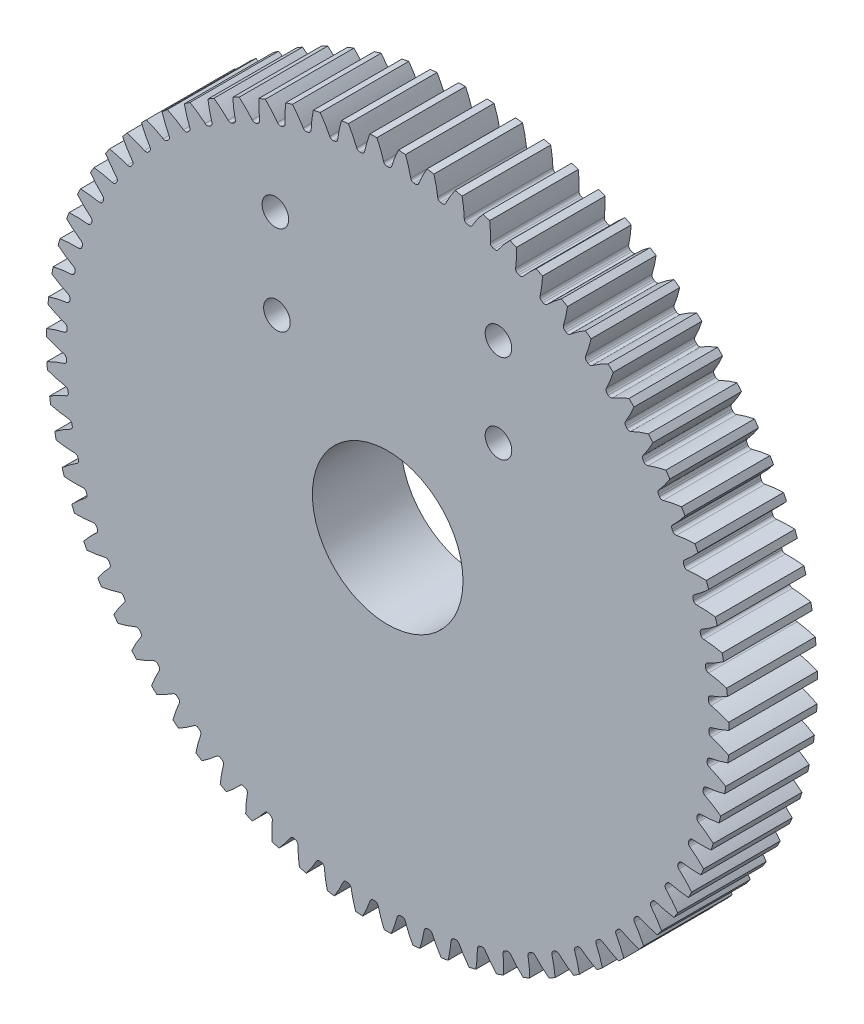
SolidWorks part; units mm, degrees
ref_plane "Front" through (0, 0, 0) normal (0, 0, 1) x (1, 0, 0)
ref_plane "Top" through (0, 0, 0) normal (0, 1, 0) x (1, 0, 0)
ref_plane "Right" through (0, 0, 0) normal (1, 0, 0) x (0, 0, -1)
ref_axis "Axis1" through (0, 0, -80.9) along (0, 0, 1)
sketch "草图1" plane through (0, 0, 0) normal (0, 0, 1) x (1, 0, 0)
  circle A0 centre (0, 0) radius 38.5
extrude "LaShenA" add sketch "草图1" along normal blind 10
sketch "SketchA" plane through (0, 0, 10) normal (0, 0, 1) x (1, 0, 0)
  line L0 (0, 0) -> (0, 38.5) construction
  arc A0 (0.0916, 36.2499) -> (-0.0916, 36.2499) centre (0, 0) ccw
  arc A1 (1.4788, 39.0083) -> (-1.4788, 39.0083) centre (0, 0) ccw
  arc A2 (-0.0916, 36.2499) -> (-0.4576, 36.5243) centre (-0.0925, 36.6299) cw
  arc A3 (0.4576, 36.5243) -> (0.0916, 36.2499) centre (0.0925, 36.6299) cw
  circle A4 centre (0, 0) radius 35.2385 construction
  circle A5 centre (0, 0) radius 38.5 construction
  circle A6 centre (0, 0) radius 36.25 construction
  circle A7 centre (0, 0) radius 37.5 construction
  spline S0 degree 3 poles (0.4576, 36.5243) (0.4608, 36.5355) (0.4704, 36.5685) (0.4866, 36.6238) (0.5068, 36.6905) (0.5279, 36.7588) (0.5499, 36.8285) (0.573, 36.8996) (0.5971, 36.9722) (0.6222, 37.0462) (0.6484, 37.1216) (0.6757, 37.1984) (0.7041, 37.2766) (0.7336, 37.3561) (0.7642, 37.437) (0.796, 37.5193) (0.829, 37.6029) (0.8632, 37.6879) (0.8986, 37.7741) (0.9352, 37.8617) (0.9731, 37.9505) (1.0123, 38.0406) (1.0528, 38.132) (1.0947, 38.2246) (1.1378, 38.3185) (1.1823, 38.4136) (1.2282, 38.5099) (1.2755, 38.6073) (1.3242, 38.706) (1.3915, 38.8401) (1.4435, 38.9409) (1.4788, 39.0083) knots 0.096666 0.096666 0.096666 0.096666 0.108398 0.131256 0.154677 0.178662 0.20321 0.228321 0.253996 0.280234 0.307036 0.334401 0.362329 0.39082 0.419875 0.449493 0.479675 0.51042 0.541728 0.5736 0.606035 0.639033 0.672595 0.70672 0.741408 0.77666 0.812475 0.848853 0.885795 0.9233 1 1 1 1
  spline S1 degree 3 poles (-0.4576, 36.5243) (-0.4608, 36.5355) (-0.4704, 36.5685) (-0.4866, 36.6238) (-0.5068, 36.6905) (-0.5279, 36.7588) (-0.5499, 36.8285) (-0.573, 36.8996) (-0.5971, 36.9722) (-0.6222, 37.0462) (-0.6484, 37.1216) (-0.6757, 37.1984) (-0.7041, 37.2766) (-0.7336, 37.3561) (-0.7642, 37.437) (-0.796, 37.5193) (-0.829, 37.6029) (-0.8632, 37.6879) (-0.8986, 37.7741) (-0.9352, 37.8617) (-0.9731, 37.9505) (-1.0123, 38.0406) (-1.0528, 38.132) (-1.0947, 38.2246) (-1.1378, 38.3185) (-1.1823, 38.4136) (-1.2282, 38.5099) (-1.2755, 38.6073) (-1.3242, 38.706) (-1.3915, 38.8401) (-1.4435, 38.9409) (-1.4788, 39.0083) knots 0.096666 0.096666 0.096666 0.096666 0.108398 0.131256 0.154677 0.178662 0.20321 0.228321 0.253996 0.280234 0.307036 0.334401 0.362329 0.39082 0.419875 0.449493 0.479675 0.51042 0.541728 0.5736 0.606035 0.639033 0.672595 0.70672 0.741408 0.77666 0.812475 0.848853 0.885795 0.9233 1 1 1 1
  dimension "D1" = 0.38
  dimension "Db" = 70.4769
  dimension "Da" = 77
  dimension "Df" = 72.5
  dimension "Dn" = 75
extrude "Cut-ExtrudeA" cut sketch "SketchA" against normal blind 30
pattern_circular "阵列(圆周)1" count 75 over 360 about axis through (0, 0, -80.9) along (0, 0, 1) of "Cut-ExtrudeA"
sketch "草图3" plane through (0, 0, 10) normal (0, 0, 1) x (1, 0, 0)
  line L0 (0, 0) -> (0, 15.5) construction
  line L1 (0, 15.5) -> (12.5, 15.5) construction
  line L2 (0, 15.5) -> (-12.5, 15.5) construction
  circle A0 centre (0, 0) radius 8.5
  circle A1 centre (-12.5, 15.5) radius 1.5
  circle A2 centre (12.5, 15.5) radius 1.5
  dimension "D1" = 15.5
  dimension "D4" = 17
  dimension "D2" = 12.5
  dimension "D3" = 12.5
extrude "切除-拉伸2" cut sketch "草图3" against normal blind 10
sketch "草图4" plane through (0, 0, 0) normal (0, 0, -1) x (-1, 0, 0)
  line L0 (-12.5, 15.5) -> (-12.5, 25.5) construction
  line L1 (-12.5, 25.5) -> (12.6729, 25.5) construction
  line L2 (12.6729, 25.5) -> (12.5, 15.5) construction
  circle A0 centre (-12.5, 25.5) radius 1.5
  circle A1 centre (12.6729, 25.5) radius 1.5
  dimension "D1" = 10
extrude "切除-拉伸3" cut sketch "草图4" against normal blind 10
